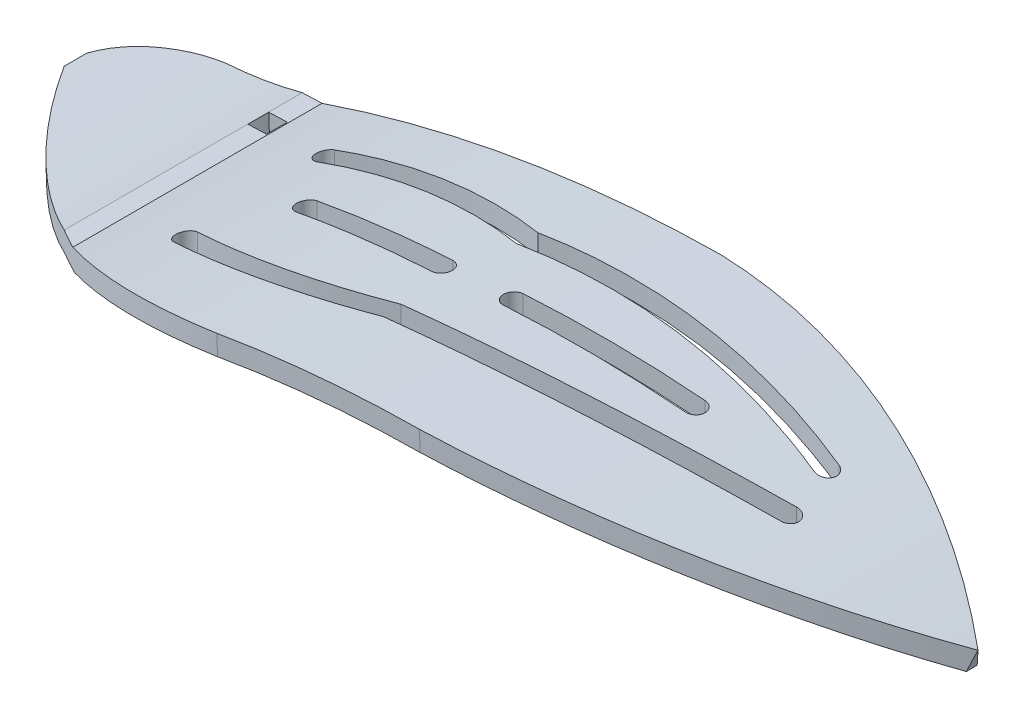
SolidWorks part; units mm, degrees
ref_plane "Front Plane" through (0, 0, 0) normal (0, 0, 1) x (1, 0, 0)
ref_plane "Top Plane" through (0, 0, 0) normal (0, 1, 0) x (1, 0, 0)
ref_plane "Right Plane" through (0, 0, 0) normal (1, 0, 0) x (0, 0, -1)
sketch "Sketch1" plane through (0, 0, 0) normal (0, 0, 1) x (1, 0, 0)
  line L0 (-75.1892, -5.0964) -> (-73.6652, -5.0437)
  line L1 (-74.9657, -6.6136) -> (-73.3855, -6.5589)
  line L2 (-86.9325, -5.9085) -> (-87.119, -7.421)
  line L3 (-12.0166, -6.0859) -> (-11.5425, -4.6375)
  arc A0 (-75.1892, -5.0964) -> (-86.9325, -5.9085) centre (-83.1525, 24.742) cw
  arc A1 (-87.6464, -5.8651) -> (-66.0194, -2.1365) centre (-84.4791, 40.3494) ccw construction
  arc A2 (-73.6652, -5.0437) -> (-11.5425, -4.6375) centre (-41.9968, -97.6861) cw
  arc A3 (-74.9657, -6.6136) -> (-87.119, -7.421) centre (-83.1525, 24.742) cw
  arc A4 (-73.3855, -6.5589) -> (-12.0166, -6.0859) centre (-41.9968, -97.6861) cw
  dimension "D1" = 1.524
extrude "Boss-Extrude1" add sketch "Sketch1" along normal blind 19.05 and the other way blind 4.191
sketch "Sketch2" plane through (0.1389, -4.0179, 0) normal (0.0345, -0.9994, 0) x (-0.9994, -0.0345, 0)
  line L0 (87.3233, 4.191) -> (75.1494, 4.191) construction
  line L1 (87.3233, 4.191) -> (87.3233, -19.05) construction
  line L2 (12.2196, -19.05) -> (73.5683, -19.05) construction
  line L3 (73.5683, 4.191) -> (12.2196, 4.191) construction
  line L4 (11.6958, 4.191) -> (11.6958, -19.05) construction
  line L5 (42.8939, -19.05) -> (58.536, -19.05)
  line L6 (81.2363, 4.191) -> (42.8939, 4.191)
  line L8 (5.8815, 12.6465) -> (93.1352, 12.6465)
  line L9 (5.8815, 12.6465) -> (5.8815, -27.1668)
  line L10 (5.8815, -27.1668) -> (93.1352, -27.1668)
  line L11 (93.1352, 12.6465) -> (93.1352, -27.1668)
  arc A0 (81.2363, 4.191) -> (87.3233, -1.9923) centre (80.6418, -2.482) cw
  arc A1 (87.3233, -1.9923) -> (58.536, -19.05) centre (57.5483, 15.437) cw
  arc A2 (42.8939, 4.191) -> (11.6958, -7.4295) centre (45.2592, -49.849) ccw
  arc A3 (11.6958, -7.4295) -> (42.8939, -19.05) centre (44.2291, 32.2245) ccw
extrude "Cut-Extrude1" cut sketch "Sketch2" against normal through all and the other way through all
sketch "Sketch3" plane through (0.1389, -4.0179, 0) normal (0.0345, -0.9994, 0) x (0.9994, 0.0345, 0)
  line L1 (-73.8796, -1.598) -> (-75.308, -1.598)
  line L2 (-73.8796, -1.598) -> (-73.8796, 0)
  line L3 (-73.8796, 0) -> (-75.308, 0)
  line L4 (-75.308, -1.598) -> (-75.308, 0)
extrude "Cut-Extrude2" cut sketch "Sketch3" against normal blind 19.05 and the other way blind 19.05
sketch "Sketch4" plane through (0, 0, 0) normal (0, 1, 0) x (1, 0, 0)
  line L0 (-64.8425, -5.837) -> (-53.6114, -6.5914) construction
  line L1 (-64.8935, -6.5973) -> (-53.6625, -7.3516)
  line L2 (-48.1635, -6.5914) -> (-34.1666, -6.5914) construction
  line L3 (-48.1635, -7.3534) -> (-34.1666, -7.3534)
  line L4 (-64.7914, -5.0767) -> (-53.5604, -5.8311)
  line L5 (-48.1635, -5.8294) -> (-34.1666, -5.8294)
  arc A0 (-68.3627, -11.6202) -> (-52.438, -11.6202) centre (-60.4003, 22.6737) ccw construction
  arc A1 (-52.438, -11.6202) -> (-24.6118, -8.9382) centre (-52.0404, 129.9442) ccw construction
  arc A2 (-25.9528, -4.6636) -> (-52.0404, -1.6463) centre (-46.8583, -71.1266) ccw construction
  arc A3 (-52.0404, -1.6463) -> (-68.3627, -0.8082) centre (-62.4466, -44.9477) ccw construction
  arc A4 (-68.535, -12.3625) -> (-52.3521, -12.3824) centre (-60.4003, 22.6737) ccw
  arc A5 (-52.3521, -12.3824) -> (-24.4642, -9.6857) centre (-52.0404, 129.9442) ccw
  arc A6 (-25.7242, -3.9368) -> (-51.9784, -0.8777) centre (-46.8583, -71.1266) ccw
  arc A7 (-51.9784, -0.8777) -> (-68.4639, -0.053) centre (-62.4466, -44.9477) ccw
  arc A8 (-68.1903, -10.8779) -> (-52.5246, -10.8579) centre (-60.4003, 22.6737) ccw
  arc A9 (-52.5246, -10.8579) -> (-24.7595, -8.1906) centre (-52.0404, 129.9442) ccw
  arc A10 (-26.1815, -5.3905) -> (-52.1028, -2.4152) centre (-46.8583, -71.1266) ccw
  arc A11 (-52.1028, -2.4152) -> (-68.2614, -1.5634) centre (-62.4466, -44.9477) ccw
  arc A12 (-64.8935, -6.5973) -> (-64.7914, -5.0767) centre (-64.8425, -5.837) cw
  arc A13 (-53.6625, -7.3516) -> (-53.5604, -5.8311) centre (-53.6114, -6.5914) ccw
  arc A14 (-48.1635, -7.3534) -> (-48.1635, -5.8294) centre (-48.1635, -6.5914) cw
  arc A15 (-34.1666, -7.3534) -> (-34.1666, -5.8294) centre (-34.1666, -6.5914) ccw
  arc A16 (-68.535, -12.3625) -> (-68.1903, -10.8779) centre (-68.3627, -11.6202) cw
  arc A17 (-24.4642, -9.6857) -> (-24.7595, -8.1906) centre (-24.6118, -8.9382) ccw
  arc A18 (-25.7242, -3.9368) -> (-26.1815, -5.3905) centre (-25.9528, -4.6636) cw
  arc A19 (-68.4639, -0.053) -> (-68.2614, -1.5634) centre (-68.3627, -0.8082) ccw
  dimension "D1" = 0.762
  dimension "D2" = 0.762
extrude "Cut-Extrude3" cut sketch "Sketch4" against normal through all and the other way through all
